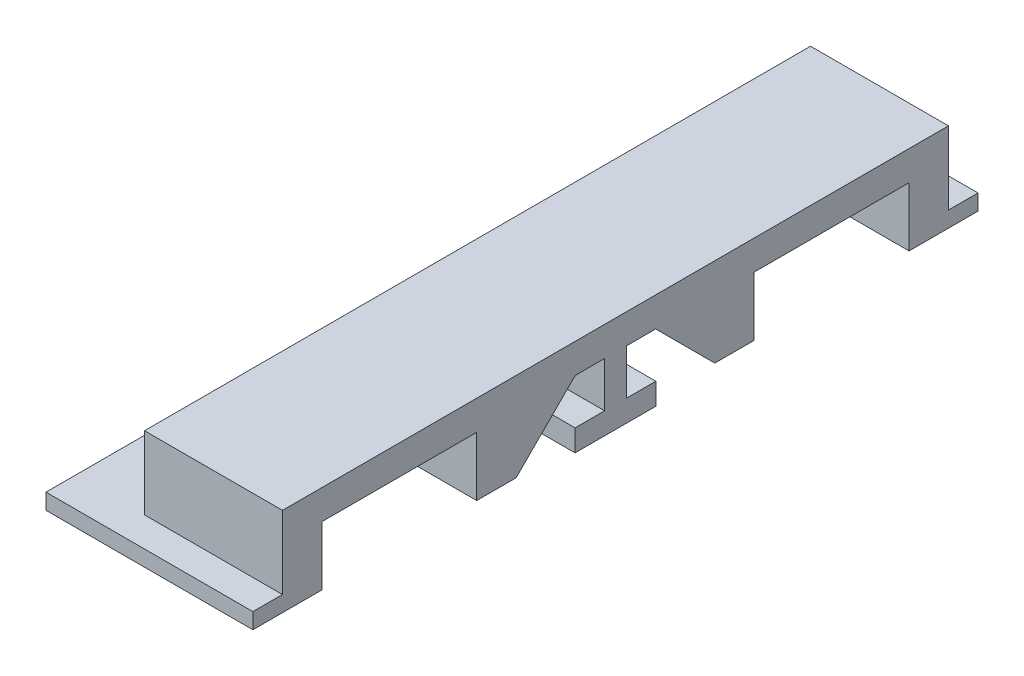
SolidWorks part; units mm, degrees
note: The reader was unsure of these and kept them because the rebuilt part matched: shared geometry of "Sketch1<3>".
ref_plane "Front Plane" through (0, 0, 0) normal (0, 0, 1) x (1, 0, 0)
ref_plane "Top Plane" through (0, 0, 0) normal (0, 1, 0) x (1, 0, 0)
ref_plane "Right Plane" through (0, 0, 0) normal (1, 0, 0) x (0, 0, -1)
sketch "Sketch1" plane through (0, 0, 0) normal (1, 0, 0) x (0, 0, -1)
  line L0 (-14.9, 4.6) -> (-7.0414, 4.6)
  line L1 (-7.0414, 4.6) -> (-7.0414, 1.6)
  line L2 (-14.9, 4.6) -> (-14.9, 1.6)
  line L3 (0, 0) -> (0, 1.2)
  line L4 (14.9, 4.6) -> (14.9, 1.6)
  line L5 (14.9, 4.6) -> (7.0414, 4.6)
  line L6 (7.0414, 4.6) -> (7.0414, 1.6)
  line L7 (-16.9, 2.4) -> (-4.2414, 2.4)
  line L8 (4.2414, 2.4) -> (16.9, 2.4)
  line L13 (0.55, 4.5) -> (0.55, 4.6)
  line L14 (-0.55, 4.6) -> (-2.0414, 4.6)
  line L15 (-0.55, 4.5) -> (-0.55, 4.6)
  line L16 (17, 2.4) -> (16.9, 2.4)
  line L20 (-0.55, 2.3) -> (-2.05, 2.3)
  line L21 (-2.05, 2.3) -> (-2.05, 1.2)
  line L22 (-0.55, 4.5) -> (-0.55, 2.3)
  line L23 (0.55, 2.3) -> (0.55, 4.5)
  line L24 (2.05, 2.3) -> (0.55, 2.3)
  line L25 (2.05, 1.2) -> (2.05, 2.3)
  line L26 (-2.05, 1.2) -> (2.05, 1.2)
  line L27 (-0.55, 2.3) -> (-2.05, 2.3)
  line L28 (-2.05, 2.3) -> (-2.05, 1.2)
  line L29 (-0.55, 4.5) -> (-0.55, 2.3)
  line L30 (0.55, 2.3) -> (0.55, 4.5)
  line L31 (2.05, 2.3) -> (0.55, 2.3)
  line L32 (2.05, 1.2) -> (2.05, 2.3)
  line L33 (-2.05, 1.2) -> (2.05, 1.2)
  line L120 (16.9, 2.4) -> (16.9, 6.1)
  line L121 (17, 3.5) -> (17, 1.5) construction
  line L123 (-17, 2.4) -> (-16.9, 2.4)
  line L124 (-16.9, 2.4) -> (-16.9, 6.1)
  line L131 (2.0414, 4.6) -> (-2.0414, 4.6)
  line L132 (-18.4, 2.4) -> (-17, 2.4)
  line L133 (-18.4, 1.6) -> (-18.4, 2.4)
  line L134 (-17, 1.6) -> (-18.4, 1.6)
  line L135 (-5.0414, 1.6) -> (-17, 1.6)
  line L136 (-2.0414, 4.6) -> (-5.0414, 1.6)
  line L137 (17, 2.4) -> (18.4, 2.4)
  line L138 (18.4, 2.4) -> (18.4, 1.6)
  line L139 (18.4, 1.6) -> (17, 1.6)
  line L140 (17, 1.6) -> (5.0414, 1.6)
  line L141 (5.0414, 1.6) -> (2.0414, 4.6)
  line L142 (2.0414, 4.6) -> (0.55, 4.6)
  line L143 (-18.4, 2.4) -> (-17, 2.4)
  line L144 (-18.4, 1.6) -> (-18.4, 2.4)
  line L145 (-17, 1.6) -> (-18.4, 1.6)
  line L146 (-5.0414, 1.6) -> (-17, 1.6)
  line L147 (-2.0414, 4.6) -> (-5.0414, 1.6)
  line L148 (17, 2.4) -> (18.4, 2.4)
  line L149 (18.4, 2.4) -> (18.4, 1.6)
  line L150 (18.4, 1.6) -> (17, 1.6)
  line L151 (17, 1.6) -> (5.0414, 1.6)
  line L152 (5.0414, 1.6) -> (2.0414, 4.6)
  line L162 (-16.9, 6.1) -> (-2.0414, 6.1)
  line L163 (-2.0414, 6.1) -> (2.0414, 6.1)
  line L164 (2.0414, 6.1) -> (16.9, 6.1)
  dimension "D3" = 0.1
  dimension "D5" = 1.5
  dimension "D6" = 1.5
  dimension "D7" = 2
  dimension "D8" = 2
  dimension "D1" = 0.2
  dimension "D2" = 0.1
extrude "Boss-Extrude1" add sketch "Sketch1" along normal blind 7 contours L164 L163 L162 L124 L123 L143 L144 L145 L146 L2 L0 L1 L147 L14 L15 L29 L27 L28 L33 L32 L31 L30 L13 L142 L152 L151 L6 L5 L4 L150 L149 L148 L16 L120 | L147 L7 L1 L146 | L146 L2 L7 L123 L143 L144 L145 | L152 L151 L6 L8 | L151 L150 L149 L148 L16 L8 L4
extrude "Boss-Extrude2" add sketch "Sketch1<3>" against normal mid plane 7 contours L152 L151 L6 L8 | L151 L150 L149 L148 L16 L8 L4 | L151 L4 L8 L6 | L146 L1 L7 L2 | L147 L7 L1 L146 | L146 L2 L7 L123 L143 L144 L145
sketch "Sketch1<3>" plane through (0, 0, 0) normal (1, 0, 0) x (0, 0, -1) same geometry as "Sketch1"
